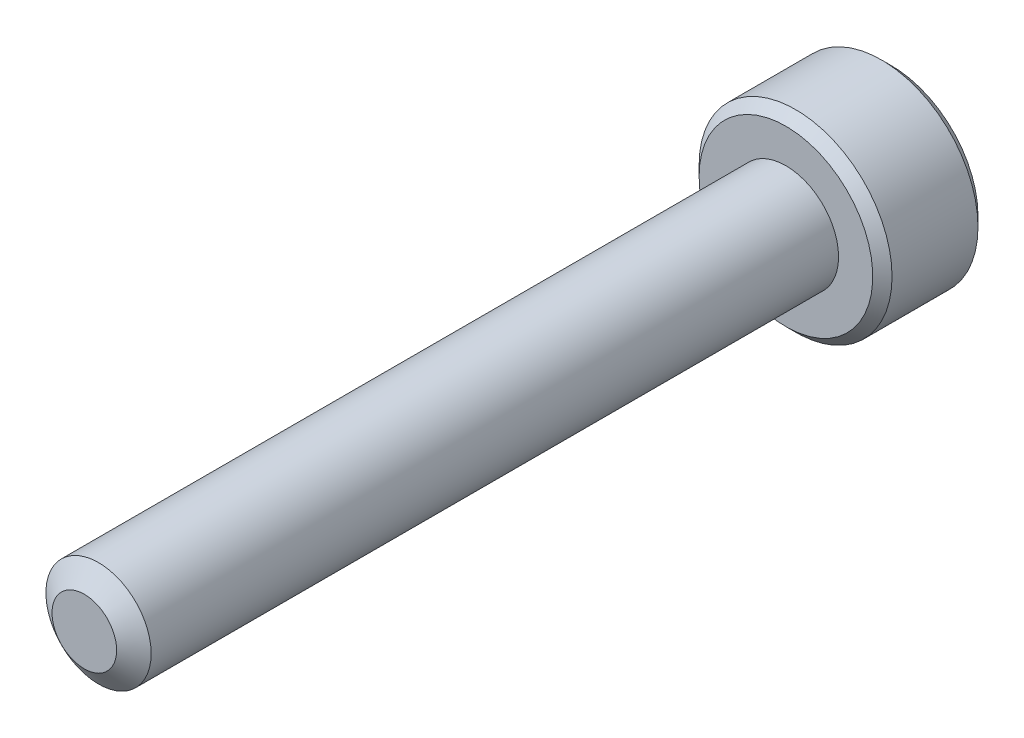
SolidWorks part; units mm, degrees
other "DetailItem1"
ref_plane "Front Plane" through (0, 0, 0) normal (0, 0, 1) x (1, 0, 0)
ref_plane "Top Plane" through (0, 0, 0) normal (0, 1, 0) x (1, 0, 0)
ref_plane "Right Plane" through (0, 0, 0) normal (1, 0, 0) x (0, 0, -1)
sketch "Sketch1" plane through (0, 0, 0) normal (0, 0, 1) x (1, 0, 0)
  circle A0 centre (0, 0) radius 1.5
  dimension "OD" = 3
extrude "Extrude1" add sketch "Sketch1" against normal blind 20
sketch "Sketch2" plane through (0, 0, 0) normal (0, 0, 1) x (1, 0, 0)
  circle A0 centre (0, 0) radius 1.5 construction
  circle A1 centre (0, 0) radius 1.5
curve "Helix/Spiral1" pitch 0.5 height 20.5 turns 41 parameters "pitch"=0.5
sketch "Sketch3" plane through (0, 0, 0) normal (1, 0, 0) x (0, 0, -1)
  line L0 (-0.4375, 1.5) -> (-0.25, 1.1752)
  line L1 (-0.25, 1.1752) -> (-0.1875, 1.1752)
  line L2 (-0.1875, 1.1752) -> (0, 1.5)
  line L3 (-0.4375, 1.5) -> (0, 1.5)
  line L4 (-0.2188, 1.5) -> (-0.2188, 1.1752) construction
  line L5 (-0.3438, 1.3376) -> (-0.0938, 1.3376) construction
  line L6 (0, 1.5) -> (0, -1.5) construction
  dimension "D1" = 0.0625
  dimension "D2" = 0.25
  dimension "D3" = 60
sweep "Cut-Sweep1" [suppressed] cut profiles "Sketch3" path "Helix/Spiral1"
sketch "Sketch4" plane through (0, 0, 0) normal (1, 0, 0) x (0, 0, -1)
  line L0 (0.4053, 1.5) -> (0, 0.9212)
  line L1 (0, 0.9212) -> (0, 1.5)
  line L2 (0.4053, 1.5) -> (0, 1.5)
  line L3 (-0.4375, 1.5) -> (0, 1.5) construction
  line L4 (0, 0) -> (7.0209, 0) construction
  dimension "D1" = 55
  dimension "D2" = 0.254
revolve "Cut-Revolve1" cut sketch "Sketch4" angle 360 about L4
sketch "Sketch6" plane through (0, 0, -20) normal (0, 0, -1) x (-1, 0, 0)
  circle A0 centre (0, 0) radius 2.75
  dimension "head dia" = 5.5
extrude "Extrude2" add sketch "Sketch6" along normal blind 3
sketch "Sketch7" plane through (0, 0, -23) normal (0, 0, -1) x (-1, 0, 0)
  line L1 (0, 1.4434) -> (-1.25, 0.7217)
  line L2 (-1.25, 0.7217) -> (-1.25, -0.7217)
  line L3 (-1.25, -0.7217) -> (0, -1.4434)
  line L4 (0, -1.4434) -> (1.25, -0.7217)
  line L5 (1.25, -0.7217) -> (1.25, 0.7217)
  line L6 (1.25, 0.7217) -> (0, 1.4434)
  circle A0 centre (0, 0) radius 1.25 construction
  dimension "hex dia" = 2.5
extrude "Cut-Extrude1" cut sketch "Sketch7" against normal blind 1.875
sketch "Sketch8" plane through (0, 0, -23) normal (0, 0, -1) x (-1, 0, 0)
  circle A0 centre (0, 0) radius 1.4434
extrude "Cut-Extrude2" cut sketch "Sketch8" against normal through all draft 45
chamfer "Chamfer1" distance 0.275 angle 45 2 edges at (-2.75, 0, -23) (-2.75, 0, -20)
sketch "Sketch10" plane through (0, 0, -20) normal (0, 0, 1) x (1, 0, 0)
  circle A1 centre (0, 0) radius 1.5
  circle A2 centre (0, 0) radius 1.5
  dimension "D1" = 0
ref_plane "Plane1" through (0, 0, 0) normal (0, 0, 1) x (1, 0, 0)
extrude "partial thread" [suppressed] add sketch "Sketch10" along normal up to surface (36 mm away) separate body up to plane "Plane1"
chamfer "Chamfer2" [suppressed] distance 0.06 angle 45
combine bodies "Combine1" [suppressed] operation type add bodies to combine 107 108
sketch "Sketch9" plane through (0, 0, 0) normal (1, 0, 0) x (0, 0, -1)
  line L0 (0, 1.5) -> (0, -1.5) construction
  line L1 (1.25, 1.5) -> (1.25, -1.5) construction
  dimension "D1" = 1.25
equation "\"D3@Helix/Spiral1\" = \"screw length@Extrude1\"+\"pitch@Helix/Spiral1\""
equation "\"D1@Sketch3\" = \"pitch@Helix/Spiral1\"*.125"
equation "\"D2@Sketch3\" = \"pitch@Helix/Spiral1\"*.5"
equation "\"D1@Cut-Extrude1\" = \"hex dia@Sketch7\"*.75"
equation "\"D1@Chamfer1\" = \"head dia@Sketch6\"*.05"
equation "\"D1@Sketch9\" = \"pitch@Helix/Spiral1\"*2.5"
equation "\"D1@Chamfer2\"=\"OD@Sketch1\"*.02"
